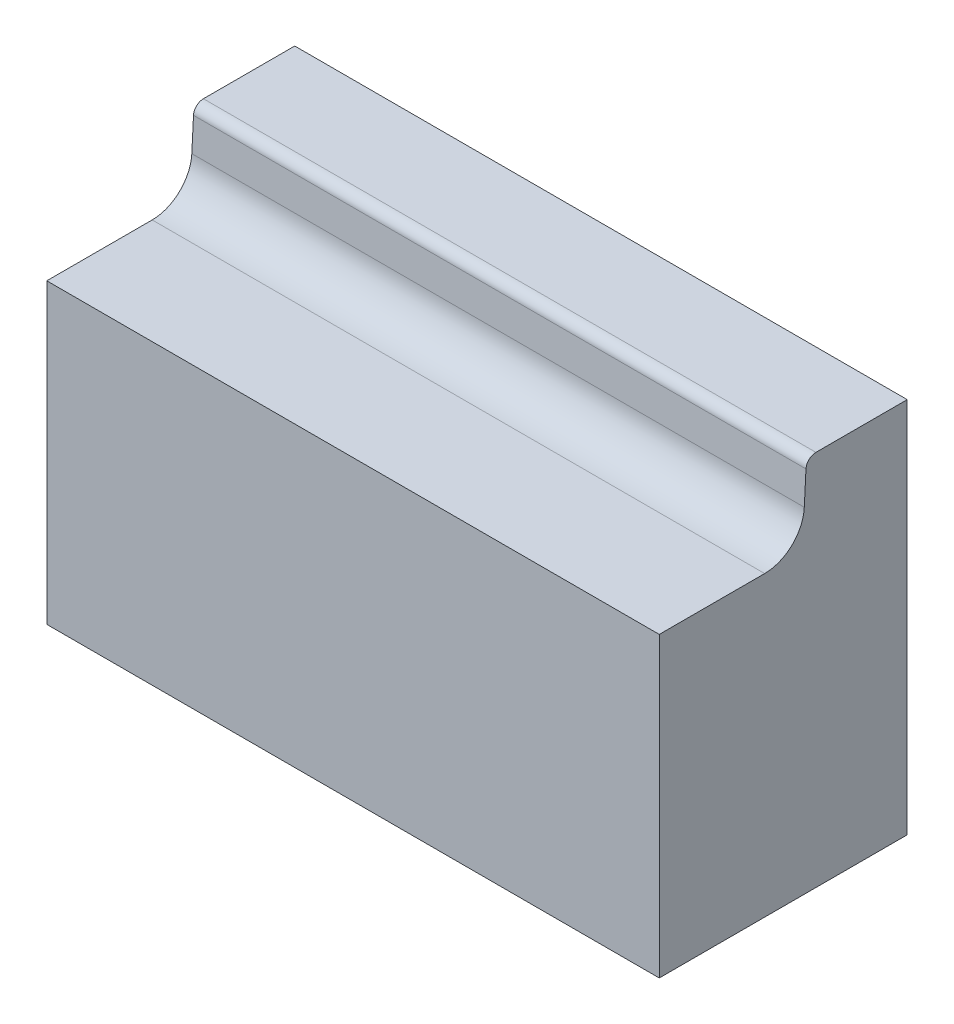
SolidWorks part; units mm, degrees
material "K110"
ref_plane "Front Plane" through (0, 0, 0) normal (0, 0, 1) x (1, 0, 0)
ref_plane "Top Plane" through (0, 0, 0) normal (0, 1, 0) x (1, 0, 0)
ref_plane "Right Plane" through (0, 0, 0) normal (1, 0, 0) x (0, 0, -1)
sketch "Sketch1" plane through (0, 0, 0) normal (0, 0, 1) x (1, 0, 0)
  line L1 (6.1065, -38) -> (67.8565, -38)
  line L2 (6.1065, -38) -> (6.1065, 0)
  line L3 (6.1065, 0) -> (67.8565, 0)
  line L4 (67.8565, -38) -> (67.8565, 0)
  dimension "D1" = 38
  dimension "D2" = 61.75
extrude "Boss-Extrude1" add sketch "Sketch1" along normal mid plane 25
sketch "Sketch2" plane through (67.8565, 0, 0) normal (1, 0, 0) x (0, 0, -1)
  line L0 (2.4945, 2.8958) -> (2.1222, -4.2093) construction
  line L1 (2.3428, 0) -> (2.1222, -4.2093)
  line L2 (-12.5, 0) -> (-12.5, -8)
  line L3 (-12.5, 0) -> (12.5, 0) construction
  line L4 (2.3428, 0) -> (-12.5, 0)
  line L5 (-12.5, -8) -> (-1.8724, -8)
  arc A0 (-1.8724, -8) -> (2.1222, -4.2093) centre (-1.8724, -4) ccw construction
  arc A1 (-1.8724, -8) -> (2.1222, -4.2093) centre (-1.8724, -4) ccw
extrude "Cut-Extrude1" cut sketch "Sketch2" against normal up to next
fillet "Fillet1" radius 1 1 edges at (36.9815, 0, -2.3428)
